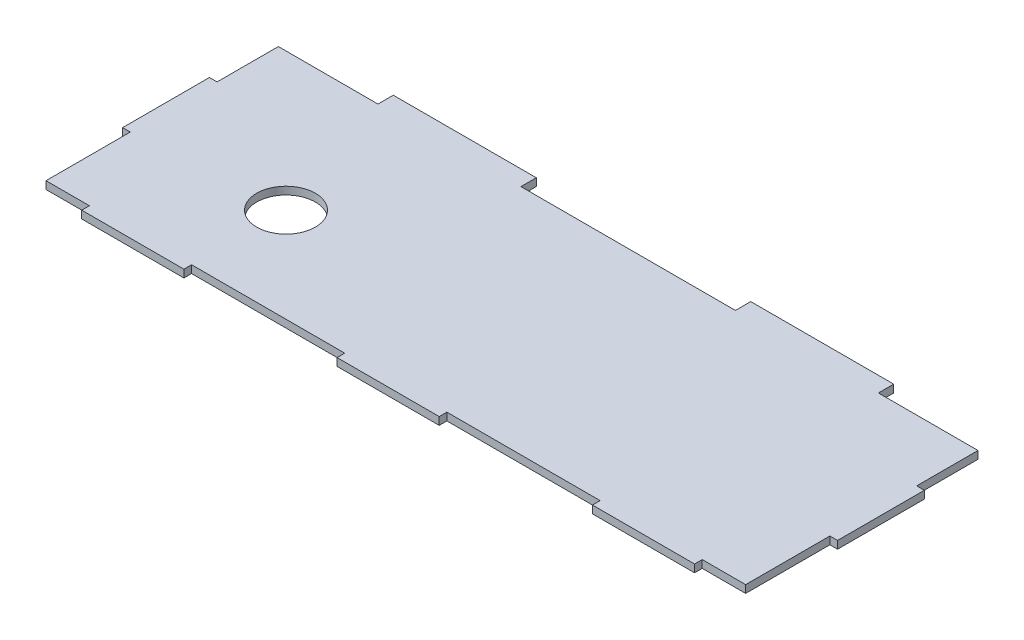
SolidWorks part; units mm, degrees
ref_plane "Front Plane" through (0, 0, 0) normal (0, 0, 1) x (1, 0, 0)
ref_plane "Top Plane" through (0, 0, 0) normal (0, 1, 0) x (1, 0, 0)
ref_plane "Right Plane" through (0, 0, 0) normal (1, 0, 0) x (0, 0, -1)
sketch "Sketch1" plane through (0, 0, 0) normal (0, 1, 0) x (1, 0, 0)
  line L0 (-70, 23.5) -> (-49, 23.5)
  line L1 (-70, -23.5) -> (70, -23.5)
  line L2 (-70, -23.5) -> (-70, 23.5)
  line L4 (70, -23.5) -> (70, 23.5)
  line L5 (-70, -23.5) -> (70, 23.5) construction
  line L6 (-70, 23.5) -> (70, -23.5) construction
  line L7 (-49, 23.5) -> (-49, 26.5)
  line L8 (-49, 26.5) -> (-21, 26.5)
  line L9 (-21, 26.5) -> (-21, 23.5)
  line L10 (-21, 23.5) -> (21, 23.5)
  line L11 (21, 23.5) -> (21, 26.5)
  line L12 (21, 26.5) -> (49, 26.5)
  line L13 (49, 26.5) -> (49, 23.5)
  line L14 (49, 23.5) -> (70, 23.5)
  point P0 (0, 0)
  dimension "D1" = 140
  dimension "D2" = 47
  dimension "D3" = 21
  dimension "D4" = 28
  dimension "D5" = 21
  dimension "D6" = 28
  dimension "D7" = 42
  dimension "D8" = 3
  dimension "D9" = 3
  dimension "D10" = 3
  dimension "D11" = 3
  dimension "D12" = 50
extrude "Boss-Extrude1" add sketch "Sketch1" along normal blind 1.5
sketch "Sketch3" plane through (0, 1.5, 0) normal (0, 1, 0) x (1, 0, 0)
  line L0 (-70, 23.5) -> (-70, -23.5) construction
  line L1 (-70, -23.5) -> (70, -23.5) construction
  circle A0 centre (-40, -3.5) radius 5.75
  dimension "D1" = 30
  dimension "D3" = 11.5
  dimension "D2" = 20
extrude "Cut-Extrude1" cut sketch "Sketch3" against normal through all
sketch "Sketch4" plane through (0, 1.5, 0) normal (0, 1, 0) x (1, 0, 0)
  line L0 (-70, 23.5) -> (-68.5, 23.5)
  line L1 (-49, 23.5) -> (-70, 23.5) construction
  line L2 (-68.5, 23.5) -> (-68.5, 11.5)
  line L3 (-68.5, 11.5) -> (-70, 11.5)
  line L4 (-70, 23.5) -> (-70, -23.5) construction
  line L5 (-70, 11.5) -> (-70, 23.5)
  line L6 (-70, -5.5) -> (-70, -23.5)
  line L7 (-70, -23.5) -> (-60, -23.5)
  line L8 (-70, -23.5) -> (70, -23.5) construction
  line L9 (-60, -23.5) -> (-60, -22)
  line L10 (-60, -22) -> (-68.5, -22)
  line L11 (-68.5, -22) -> (-68.5, -5.5)
  line L12 (-68.5, -5.5) -> (-70, -5.5)
  line L13 (-40, -23.5) -> (-40, -22)
  line L14 (-40, -22) -> (-10, -22)
  line L15 (-10, -22) -> (-10, -23.5)
  line L16 (-10, -23.5) -> (-40, -23.5)
  line L17 (10, -23.5) -> (10, -22)
  line L18 (10, -22) -> (40, -22)
  line L19 (40, -22) -> (40, -23.5)
  line L20 (40, -23.5) -> (10, -23.5)
  line L21 (60, -23.5) -> (70, -23.5)
  line L22 (70, -23.5) -> (70, -5.5)
  line L23 (70, -23.5) -> (70, 23.5) construction
  line L24 (70, -5.5) -> (68.5, -5.5)
  line L25 (68.5, -5.5) -> (68.5, -22)
  line L26 (68.5, -22) -> (60, -22)
  line L27 (60, -22) -> (60, -23.5)
  line L33 (70, 23.5) -> (68.5, 23.5)
  line L34 (68.5, 23.5) -> (68.5, 11.5)
  line L35 (68.5, 11.5) -> (70, 11.5)
  line L36 (70, 11.5) -> (70, 23.5)
  dimension "D1" = 1.5
  dimension "D2" = 12
  dimension "D3" = 18
  dimension "D4" = 1.5
  dimension "D5" = 1.5
  dimension "D6" = 10
  dimension "D7" = 20
  dimension "D8" = 30
  dimension "D9" = 30
  dimension "D10" = 10
  dimension "D11" = 1.5
  dimension "D12" = 1.5
  dimension "D13" = 18
  dimension "D14" = 1.5
  dimension "D15" = 12
  dimension "D16" = 20
  dimension "D17" = 1.5
  dimension "D18" = 1.5
extrude "Cut-Extrude2" cut sketch "Sketch4" against normal through all
